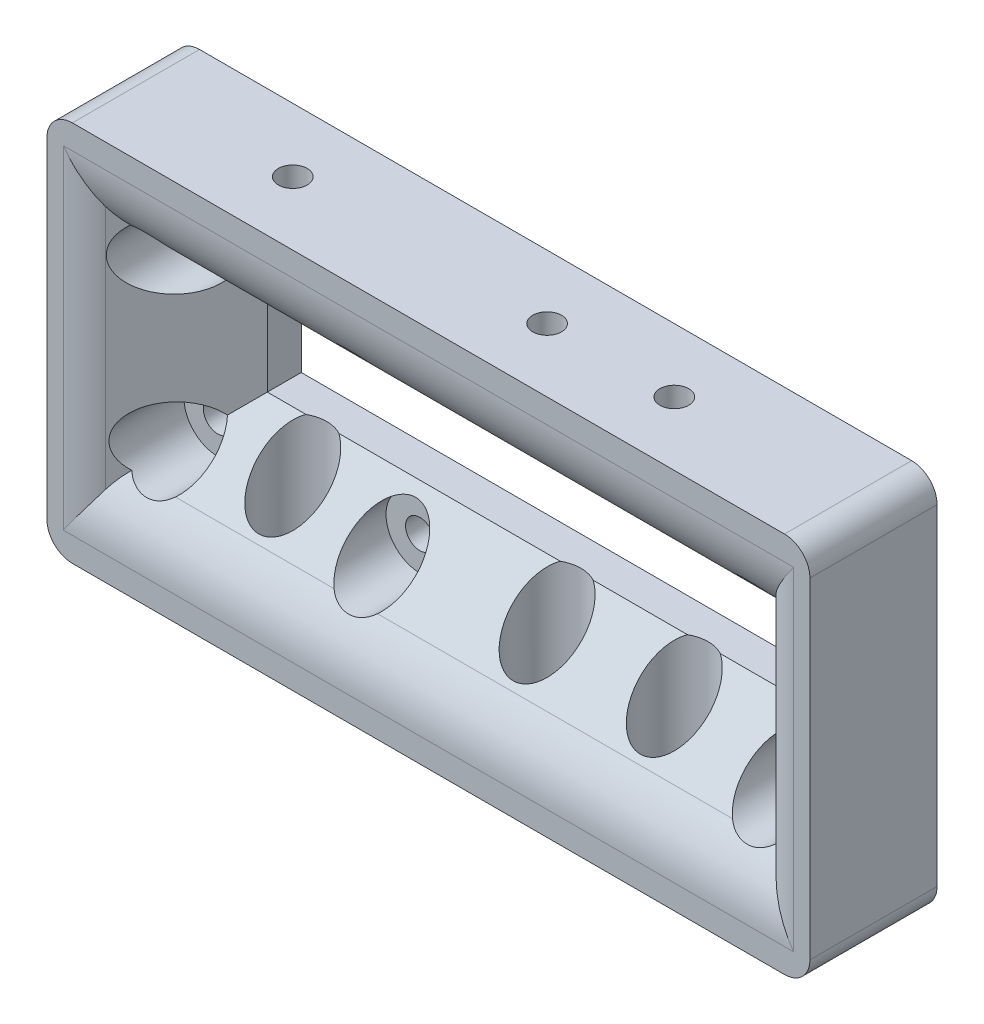
SolidWorks part; units mm, degrees
material "ABS"
ref_plane "Front" through (0, 0, 0) normal (0, 0, 1) x (1, 0, 0)
ref_plane "Top" through (0, 0, 0) normal (0, 1, 0) x (1, 0, 0)
ref_plane "Right" through (0, 0, 0) normal (1, 0, 0) x (0, 0, -1)
sketch "Sketch1" plane through (0, 0, 0) normal (0, 0, 1) x (1, 0, 0)
  line L1 (-45, -22.5) -> (45, -22.5)
  line L2 (-45, -22.5) -> (-45, 22.5)
  line L3 (-45, 22.5) -> (45, 22.5)
  line L4 (45, -22.5) -> (45, 22.5)
  line L5 (-45, -22.5) -> (45, 22.5) construction
  line L6 (-45, 22.5) -> (45, -22.5) construction
  point P0 (0, 0)
extrude "Boss-Extrude1" add sketch "Sketch1" along normal blind 15
hole_wizard "CBORE for M3 SBHCS1" positions "Sketch3" profile "Sketch2" counterbore size "M3" standard "ANSI Metric" end condition through all
sketch "Sketch3" plane through (0, 0, 15) normal (0, 0, 1) x (1, 0, 0)
  line L0 (-45, 22.5) -> (-45, -22.5) construction
  line L1 (45, -22.5) -> (45, 22.5) construction
  line L2 (-35.5, 9.5) -> (-11.5, 9.5) construction
  line L3 (-11.5, 9.5) -> (35.5, 9.5) construction
  line L5 (-35.5, 9.5) -> (-35.3428, -9.5) construction
  line L7 (-35.3428, -9.5) -> (-11.5, -9.5) construction
  line L8 (-11.5, -9.5) -> (35.5, -9.5) construction
  line L9 (-11.5, 9.5) -> (-11.5, -9.5) construction
  line L11 (35.5, 9.5) -> (35.5, -9.5) construction
  line L13 (45, 22.5) -> (-45, 22.5) construction
  line L14 (-45, -22.5) -> (45, -22.5) construction
  point P0 (-35.5, 9.5)
  point P2 (-35.3428, -9.5)
  point P4 (-11.5, -9.5)
  point P6 (-11.5, 9.5)
  point P8 (35.5, 9.5)
  point P10 (35.5, -9.5)
  dimension "D1" = 24
  dimension "D2" = 47
  dimension "D3" = 9.5
  dimension "D4" = 9.5
  dimension "D5" = 19
  dimension "D6" = 13
  dimension "D7" = 13
sketch "Sketch2" plane through (-35.5, 9.5, 15) normal (1, 0, 0) x (0, -1, 0)
  line L0 (0, 0) -> (0, 15)
  line L1 (0, 15) -> (1.7, 15)
  line L3 (1.7, 15) -> (1.7, 10.5)
  line L4 (1.7, 10.5) -> (4, 10.5)
  line L5 (4, 10.5) -> (4, 0)
  line L7 (4, 0) -> (0, 0)
  line L11 (0, -6.35) -> (0, 107.95) construction
  dimension "Thru Hole Dia." = 3.4
  dimension "Thru Hole Depth" = 15
  dimension "C'Bore Dia." = 8
  dimension "C'Bore Depth" = 10.5
sketch "Sketch4" plane through (0, 0, 15) normal (0, 0, 1) x (1, 0, 0)
  line L0 (-45, 22.5) -> (-45, -22.5) construction
  line L1 (-30, 4.5) -> (30, 4.5)
  line L2 (-30, 4.5) -> (-30, -4.5)
  line L3 (-30, -4.5) -> (30, -4.5)
  line L4 (30, 4.5) -> (30, -4.5)
  line L5 (-45, -22.5) -> (45, -22.5) construction
  line L6 (45, 22.5) -> (-45, 22.5) construction
  line L7 (45, -22.5) -> (45, 22.5) construction
  dimension "D1" = 15
  dimension "D2" = 18
  dimension "D3" = 18
  dimension "D4" = 15
extrude "Cut-Extrude1" cut sketch "Sketch4" against normal through all
hole_wizard "CBORE for M3 SBHCS2" positions "Sketch6" profile "Sketch5" counterbore size "M3" standard "ANSI Metric" end condition through all
sketch "Sketch6" plane through (0, -4.5, 0) normal (0, 1, 0) x (1, 0, 0)
  line L0 (-30, 0) -> (30, 0) construction
  line L1 (-23.5, -7.5) -> (28.459, -7.5) construction
  line L3 (-30, 0) -> (-30, -15) construction
  point P0 (-23.5, -7.5)
  point P2 (6.5, -7.5)
  point P11 (-30, -7.5)
  point P17 (21.5, -7.5)
  dimension "D1" = 7.5
  dimension "D2" = 7.5
  dimension "D3" = 6.5
  dimension "D4" = 30
  dimension "D5" = 15
sketch "Sketch5" plane through (-23.5, -4.5, 7.5) normal (1, 0, 0) x (0, 0, 1)
  line L0 (0, 0) -> (0, 18)
  line L1 (0, 18) -> (1.7, 18)
  line L3 (1.7, 18) -> (1.7, 13.5)
  line L4 (1.7, 13.5) -> (4, 13.5)
  line L5 (4, 13.5) -> (4, 0)
  line L7 (4, 0) -> (0, 0)
  line L11 (0, -6.35) -> (0, 107.95) construction
  dimension "Thru Hole Dia." = 3.4
  dimension "Thru Hole Depth" = 18
  dimension "C'Bore Dia." = 8
  dimension "C'Bore Depth" = 13.5
hole_wizard "CBORE for M3 SBHCS3" positions "Sketch8" profile "Sketch7" counterbore size "M3" standard "ANSI Metric" end condition through all
sketch "Sketch8" plane through (0, 4.5, 0) normal (0, -1, 0) x (-1, 0, 0)
  line L0 (23.5, -7.5) -> (-28.0558, -7.5) construction
  line L2 (-30, -15) -> (30, -15) construction
  line L3 (30, 0) -> (30, -15) construction
  point P0 (23.5, -7.5)
  point P2 (-6.5, -7.5)
  point P4 (-21.5, -7.5)
  dimension "D1" = 7.5
  dimension "D2" = 6.5
  dimension "D3" = 30
  dimension "D4" = 15
sketch "Sketch7" plane through (-23.5, 4.5, 7.5) normal (1, 0, 0) x (0, 0, -1)
  line L0 (0, 0) -> (0, 18)
  line L1 (0, 18) -> (1.7, 18)
  line L3 (1.7, 18) -> (1.7, 13.5)
  line L4 (1.7, 13.5) -> (4, 13.5)
  line L5 (4, 13.5) -> (4, 0)
  line L7 (4, 0) -> (0, 0)
  line L11 (0, -6.35) -> (0, 107.95) construction
  dimension "Thru Hole Dia." = 3.4
  dimension "Thru Hole Depth" = 18
  dimension "C'Bore Dia." = 8
  dimension "C'Bore Depth" = 13.5
chamfer "Chamfer1" distance 11 angle 45 1 edges at (0, -4.5, 15)
chamfer "Chamfer2" distance 11 angle 45 1 edges at (0, 4.5, 15)
chamfer "Chamfer5" distance 11 angle 45 1 edges at (-30, 0, 15)
chamfer "Chamfer6" distance 11 angle 45 1 edges at (30, 0, 15)
fillet "Fillet1" radius 10 1 edges at (0, 15.5, 15)
fillet "Fillet2" radius 5 1 edges at (-41, 2.0711, 15)
fillet "Fillet3" radius 5 1 edges at (41, 2.0711, 15)
fillet "Fillet4" radius 10 1 edges at (0, -15.5, 15)
fillet "Fillet5" radius 3 4 edges at (45, -22.5, 7.5) (45, 22.5, 7.5) (-45, 22.5, 7.5) (-45, -22.5, 7.5)
